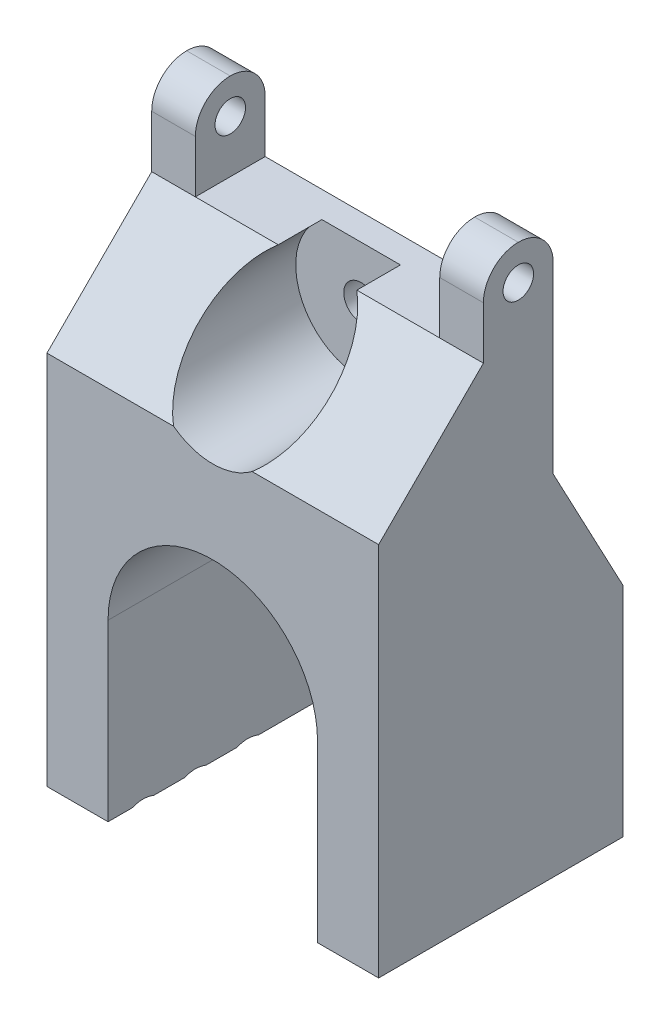
SolidWorks part; units mm, degrees
ref_plane "Front Plane" through (0, 0, 0) normal (0, 0, 1) x (1, 0, 0)
ref_plane "Top Plane" through (0, 0, 0) normal (0, 1, 0) x (1, 0, 0)
ref_plane "Right Plane" through (0, 0, 0) normal (1, 0, 0) x (0, 0, -1)
sketch "Sketch1" plane through (0, 0, 0) normal (0, 0, 1) x (1, 0, 0)
  line L1 (-19, -27.5) -> (19, -27.5)
  line L2 (-19, -27.5) -> (-19, 27.5)
  line L3 (-19, 27.5) -> (19, 27.5)
  line L4 (19, -27.5) -> (19, 27.5)
  line L5 (-19, -27.5) -> (19, 27.5) construction
  line L6 (-19, 27.5) -> (19, -27.5) construction
  point P0 (0, 0)
  dimension "D1" = 38
  dimension "D2" = 55
extrude "Boss-Extrude1" add sketch "Sketch1" along normal blind 20
sketch "Sketch2" plane through (0, 0, 20) normal (0, 0, 1) x (1, 0, 0)
  line L0 (-19, -27.5) -> (19, -27.5) construction
  line L1 (-12, -27.5) -> (12, -27.5)
  line L2 (-12, -27.5) -> (-12, -7.5)
  line L3 (-12, -7.5) -> (12, -7.5) construction
  line L4 (12, -27.5) -> (12, -7.5)
  line L5 (0, -7.5) -> (0, 0) construction
  arc A0 (-12, -7.5) -> (12, -7.5) centre (0, -7.5) cw
  dimension "D1" = 24
  dimension "D2" = 20
extrude "Cut-Extrude1" cut sketch "Sketch2" against normal through all
sketch "Sketch3" plane through (0, -27.5, 0) normal (0, -1, 0) x (1, 0, 0)
  line L0 (-15, 16) -> (15, 16) construction
  line L1 (0, 16) -> (0, 0) construction
  line L2 (12, 20) -> (-12, 20) construction
  circle A0 centre (-15, 16) radius 2.25
  circle A1 centre (15, 16) radius 2.25
  dimension "D1" = 4.5
  dimension "D2" = 30
  dimension "D3" = 4
extrude "Cut-Extrude2" cut sketch "Sketch3" against normal blind 20
pattern_linear "LPattern1" count 3 spacing 6 along (0, 0, -1) of "Cut-Extrude2"
chamfer "Chamfer1" distance 12 angle 45 1 edges at (0, 27.5, 20)
sketch "Sketch4" plane through (0, 27.5, 0) normal (0, 1, 0) x (1, 0, 0)
  line L0 (-19, -8) -> (19, -8) construction
  line L1 (-19, 0) -> (-14, 0)
  line L2 (-19, 0) -> (-19, -8)
  line L3 (-19, -8) -> (-14, -8)
  line L4 (-14, 0) -> (-14, -8)
  dimension "D1" = 5
extrude "Boss-Extrude2" add sketch "Sketch4" along normal blind 10
fillet "Fillet1" radius 4 2 edges at (-16.5, 37.5, 0) (-16.5, 37.5, 8)
sketch "Sketch5" plane through (-19, 0, 0) normal (-1, 0, 0) x (0, 0, 1)
  circle A0 centre (4, 33.5) radius 1.75
  dimension "D1" = 3.5
extrude "Cut-Extrude3" cut sketch "Sketch5" against normal through all
mirror "Mirror1" about plane through (0, 0, 0) normal (1, 0, 0) of "Cut-Extrude3", "Fillet1", "Boss-Extrude2"
chamfer "Chamfer2" distance 1 angle 45 6 edges at (15, -27.5, 13.75) (15, -27.5, 7.75) (15, -27.5, 1.75) (-15, -27.5, 1.75) (-15, -27.5, 7.75) (-15, -27.5, 13.75)
sketch "Sketch6" plane through (0, 0, 20) normal (0, 0, 1) x (1, 0, 0)
  line L0 (14, 33.5) -> (-14, 33.5) construction
  line L1 (0, 33.5) -> (0, 21.5) construction
  circle A0 centre (0, 21.5) radius 7.5
  dimension "D2" = 15
  dimension "D1" = 12
extrude "Cut-Extrude4" cut sketch "Sketch6" against normal blind 17
sketch "Sketch7" plane through (0, 0, 3) normal (0, 0, 1) x (1, 0, 0)
  circle A0 centre (0, 21.5) radius 2
  dimension "D1" = 4
extrude "Cut-Extrude5" cut sketch "Sketch7" against normal through all and the other way through all
sketch "Sketch8" plane through (0, 0, 0) normal (0, 0, -1) x (-1, 0, 0)
  line L0 (-12, -27.5) -> (-12, -7.5) construction
  line L1 (-19, -27.5) -> (-12, -27.5)
  line L2 (-19, -27.5) -> (-19, 12.5)
  line L3 (-19, 12.5) -> (-12, 12.5)
  line L4 (-12, -27.5) -> (-12, 12.5)
  line L5 (19, 33.5) -> (19, -27.5) construction
  line L6 (12, -27.5) -> (19, -27.5)
  line L7 (12, -27.5) -> (12, 12.5)
  line L8 (12, 12.5) -> (19, 12.5)
  line L9 (19, -27.5) -> (19, 12.5)
  line L10 (-12, 12.5) -> (12, 12.5) construction
  dimension "D1" = 40
extrude "Boss-Extrude3" add sketch "Sketch8" along normal blind 8
chamfer "Chamfer3" distance 8 angle 62 2 edges at (-15.5, 12.5, -8) (15.5, 12.5, -8) first distance on face at (-15.5, 12.5, -4) first distance on face at (15.5, 12.5, -4)
